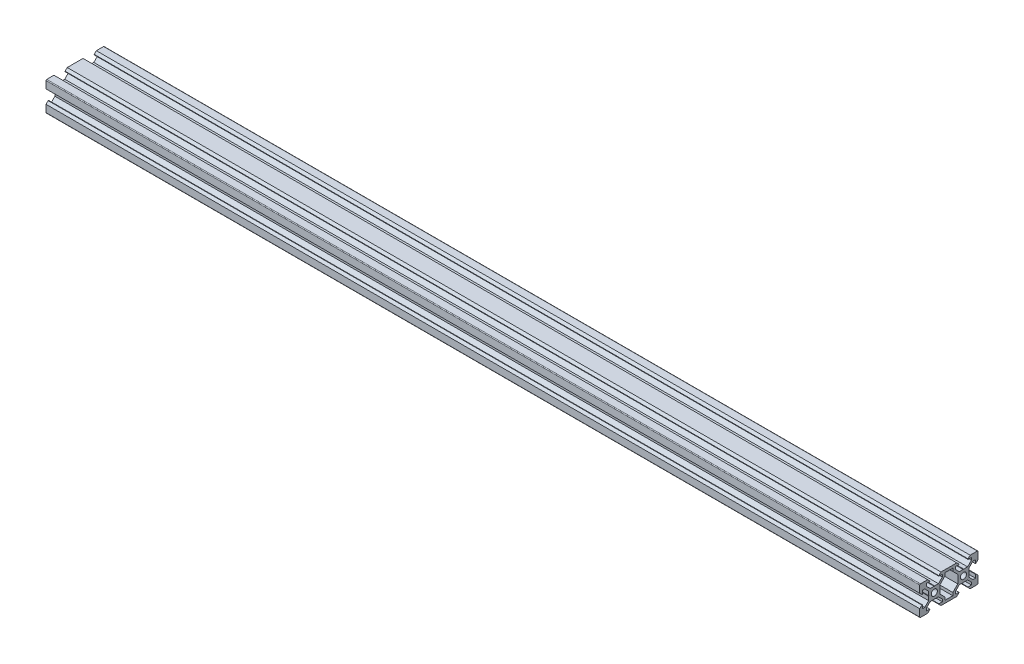
SolidWorks part; units mm, degrees
material "6061-T6 (SS)"
ref_plane "Top" through (0, 0, 0) normal (0, 0, 1) x (1, 0, 0)
ref_plane "Front" through (0, 0, 0) normal (0, 1, 0) x (1, 0, 0)
ref_plane "Right" through (0, 0, 0) normal (1, 0, 0) x (0, 0, -1)
sketch "Profile Sketch" plane through (0, 0, 0) normal (1, 0, 0) x (0, 0, -1)
  line L0 (5.42, 10) -> (-5.42, 10)
  line L1 (-4.5, 8.2) -> (-4.5, 6.56)
  line L2 (-4.5, 6.56) -> (-7.16, 3.9)
  line L3 (-7.16, 3.9) -> (-9.79, 3.9)
  line L4 (-9.79, 3.9) -> (-10, 3.69)
  line L5 (2.7, 8.2) -> (-2.7, 8.2)
  line L6 (-2.7, 8.2) -> (-2.7, 6.2387)
  line L7 (-2.7, 6.2387) -> (-6.1, 2.8387)
  line L8 (-6.1, 2.8387) -> (-6.1, -0.21)
  line L9 (-6.875, 8.545) -> (-6.875, 8.2)
  line L10 (-6.875, 8.2) -> (-4.5, 8.2)
  line L11 (-6.875, 8.545) -> (-5.42, 10)
  line L12 (0, -10) -> (0, 10) construction
  line L13 (-20, 0) -> (20, 0) construction
  line L14 (-10, -10) -> (-10, 10) construction
  line L15 (-6.875, -8.545) -> (-5.42, -10)
  line L16 (-6.875, -8.2) -> (-4.5, -8.2)
  line L17 (-6.875, -8.545) -> (-6.875, -8.2)
  line L18 (-2.7, -6.2387) -> (-6.1, -2.8387)
  line L19 (-2.7, -8.2) -> (-2.7, -6.2387)
  line L20 (2.7, -8.2) -> (-2.7, -8.2)
  line L21 (-7.16, -3.9) -> (-9.79, -3.9)
  line L22 (-4.5, -6.56) -> (-7.16, -3.9)
  line L23 (-4.5, -8.2) -> (-4.5, -6.56)
  line L24 (5.42, -10) -> (-5.42, -10)
  line L25 (-10, 0) -> (-20, 10) construction
  line L26 (-18.545, 3.125) -> (-18.2, 3.125)
  line L27 (-13.125, -8.545) -> (-13.125, -8.2)
  line L28 (-13.125, -8.2) -> (-15.5, -8.2)
  line L29 (-13.125, -8.545) -> (-14.58, -10)
  line L30 (-15.5, -8.2) -> (-15.5, -6.56)
  line L31 (-15.5, -6.56) -> (-12.84, -3.9)
  line L32 (-12.84, -3.9) -> (-10.21, -3.9)
  line L33 (-20, 4.58) -> (-20, 9.5)
  line L34 (-13.9, 2.8387) -> (-13.9, 0.21)
  line L35 (-16.56, 5.5) -> (-13.9, 2.8387)
  line L36 (-12.84, 3.9) -> (-10.21, 3.9)
  line L37 (-15.5, 6.56) -> (-12.84, 3.9)
  line L38 (-15.5, 8.2) -> (-15.5, 6.56)
  line L39 (-13.125, 8.545) -> (-14.58, 10)
  line L40 (-13.125, 8.2) -> (-15.5, 8.2)
  line L41 (-13.125, 8.545) -> (-13.125, 8.2)
  line L42 (-18.2, 3.125) -> (-18.2, 5.5)
  line L43 (-18.545, 3.125) -> (-20, 4.58)
  line L44 (-18.2, 5.5) -> (-16.56, 5.5)
  line L45 (-14.58, 10) -> (-19.5, 10)
  line L46 (-16.56, -5.5) -> (-13.9, -2.8387)
  line L47 (-14.58, -10) -> (-19.5, -10)
  line L48 (-18.2, -5.5) -> (-16.56, -5.5)
  line L49 (-18.545, -3.125) -> (-20, -4.58)
  line L50 (-18.2, -3.125) -> (-18.2, -5.5)
  line L51 (-20, -4.58) -> (-20, -9.5)
  line L52 (-18.545, -3.125) -> (-18.2, -3.125)
  line L53 (10, -10) -> (10, 10) construction
  line L54 (18.545, -3.125) -> (18.2, -3.125)
  line L55 (20, -4.58) -> (20, -9.5)
  line L56 (18.2, -3.125) -> (18.2, -5.5)
  line L57 (18.545, -3.125) -> (20, -4.58)
  line L58 (18.2, -5.5) -> (16.56, -5.5)
  line L59 (14.58, -10) -> (19.5, -10)
  line L60 (16.56, -5.5) -> (13.9, -2.8387)
  line L61 (14.58, 10) -> (19.5, 10)
  line L62 (18.2, 5.5) -> (16.56, 5.5)
  line L63 (18.545, 3.125) -> (20, 4.58)
  line L64 (18.2, 3.125) -> (18.2, 5.5)
  line L65 (13.125, 8.545) -> (13.125, 8.2)
  line L66 (13.125, 8.2) -> (15.5, 8.2)
  line L67 (13.125, 8.545) -> (14.58, 10)
  line L68 (15.5, 8.2) -> (15.5, 6.56)
  line L69 (15.5, 6.56) -> (12.84, 3.9)
  line L70 (12.84, 3.9) -> (10.21, 3.9)
  line L71 (16.56, 5.5) -> (13.9, 2.8387)
  line L72 (13.9, 2.8387) -> (13.9, 0.21)
  line L73 (20, 4.58) -> (20, 9.5)
  line L74 (12.84, -3.9) -> (10.21, -3.9)
  line L75 (15.5, -6.56) -> (12.84, -3.9)
  line L76 (15.5, -8.2) -> (15.5, -6.56)
  line L77 (13.125, -8.545) -> (14.58, -10)
  line L78 (13.125, -8.2) -> (15.5, -8.2)
  line L79 (13.125, -8.545) -> (13.125, -8.2)
  line L80 (18.545, 3.125) -> (18.2, 3.125)
  line L81 (4.5, -8.2) -> (4.5, -6.56)
  line L82 (4.5, -6.56) -> (7.16, -3.9)
  line L83 (7.16, -3.9) -> (9.79, -3.9)
  line L84 (2.7, -8.2) -> (2.7, -6.2387)
  line L85 (2.7, -6.2387) -> (6.1, -2.8387)
  line L86 (6.875, -8.545) -> (6.875, -8.2)
  line L87 (6.875, -8.2) -> (4.5, -8.2)
  line L88 (6.875, -8.545) -> (5.42, -10)
  line L89 (6.875, 8.545) -> (5.42, 10)
  line L90 (6.875, 8.2) -> (4.5, 8.2)
  line L91 (6.875, 8.545) -> (6.875, 8.2)
  line L92 (6.1, 2.8387) -> (6.1, -0.21)
  line L93 (2.7, 6.2387) -> (6.1, 2.8387)
  line L94 (2.7, 8.2) -> (2.7, 6.2387)
  line L95 (9.79, 3.9) -> (10, 3.69)
  line L96 (7.16, 3.9) -> (9.79, 3.9)
  line L97 (4.5, 6.56) -> (7.16, 3.9)
  line L98 (4.5, 8.2) -> (4.5, 6.56)
  line L99 (-10, 3.69) -> (-10.21, 3.9)
  line L100 (-10, -3.69) -> (-10.21, -3.9)
  line L101 (-9.79, -3.9) -> (-10, -3.69)
  line L102 (-13.9, -0.21) -> (-13.69, 0)
  line L103 (-13.69, 0) -> (-13.9, 0.21)
  line L104 (-13.9, -0.21) -> (-13.9, -2.8387)
  line L105 (-6.1, -0.21) -> (-6.31, 0)
  line L106 (-6.31, 0) -> (-6.1, -0.21)
  line L107 (-6.1, -0.21) -> (-6.1, -2.8387)
  line L108 (6.31, 0) -> (6.1, -0.21)
  line L109 (6.1, -0.21) -> (6.31, 0)
  line L110 (13.69, 0) -> (13.9, 0.21)
  line L111 (13.9, -0.21) -> (13.69, 0)
  line L112 (9.79, -3.9) -> (10, -3.69)
  line L113 (10, -3.69) -> (10.21, -3.9)
  line L114 (10, 3.69) -> (10.21, 3.9)
  line L115 (6.1, -0.21) -> (6.1, -2.8387)
  line L116 (13.9, -0.21) -> (13.9, -2.8387)
  line L118 (20, -10) -> (20, 10) construction
  line L119 (20, -10) -> (-20, -10) construction
  line L120 (-20, -10) -> (-20, 10) construction
  line L121 (20, 10) -> (-20, 10) construction
  line L122 (20, -10) -> (-20, 10) construction
  line L123 (-20, -10) -> (20, 10) construction
  circle A0 centre (-10, 0) radius 2.1
  arc A1 (-19.5, 10) -> (-20, 9.5) centre (-19.5, 9.5) ccw
  arc A2 (-19.5, -10) -> (-20, -9.5) centre (-19.5, -9.5) cw
  arc A3 (19.5, -10) -> (20, -9.5) centre (19.5, -9.5) ccw
  arc A4 (19.5, 10) -> (20, 9.5) centre (19.5, 9.5) cw
  circle A5 centre (10, 0) radius 2.1
  point P35 (-2.4957, 0)
  point P108 (0, -8.2)
  point P119 (0, 8.2)
  point P123 (2.4957, 0)
  point P131 (0, 0)
  point P143 (0, 0)
  dimension "D4" = 5.42
  dimension "D5" = 40
  dimension "D6" = 4.2
  dimension "D16" = 0.5
  dimension "D1" = 0.21
  dimension "D2" = 45
  dimension "D3" = 20
  dimension "D7" = 1.5
  dimension "D8" = 1.8
  dimension "D9" = 10
  dimension "D10" = 3.9
  dimension "D11" = 3.9
  dimension "D12" = 1.8
  dimension "D13" = 3.125
  dimension "D14" = 5.5
  dimension "D15" = 1.64
  dimension "D17" = 5.4
extrude "Profile Extrude" add sketch "Profile Sketch" along normal blind 600 contours A4 L61 L67 L65 L66 L68 L69 L70 L114 L95 L96 L97 L98 L90 L91 L89 L0 L11 L9 L10 L1 L2 L3 L4 L99 L36 L37 L38 L40 L41 L39 L45 A1 L33 L43 L26 L42 L44 L35 L34 L103 L102 L104 L46 L48 L50 L52 L49 L51 A2 L47 region at (0, 8.9563, -5.8313)
equation "\"M2x0.4_Close_Hole\"= 2.2"
equation "\"M2.5x0.45_Close_Hole\"= 2.7"
equation "\"M3x0.5_Close_Hole\"= 3.2"
equation "\"M4x0.7_Close_Hole\"= 4.3"
equation "\"M5x0.8_Close_Hole\"= 5.3"
equation "\"M6x1_Close_Hole\"= 6.3"
equation "\"M7x1_Close_Hole\"= 7.4"
equation "\"M8x1.25_Close_Hole\"= 8.4"
equation "\"M2x0.4_Tap_Hole_75\"= 1.6"
equation "\"M3x0.5_Tap_Hole_75\"= 2.5"
equation "\"M4x0.7_Tap_Hole_75\"= 3.3"
equation "\"M5x0.8_Tap_Hole_75\"= 4.2"
equation "\"M6x1_Tap_Hole_75\"= 5"
equation "\"M7x1_Tap_Hole_75\"= 6"
equation "\"M8x1.25_Tap_Hole_75\"= 6.8"
